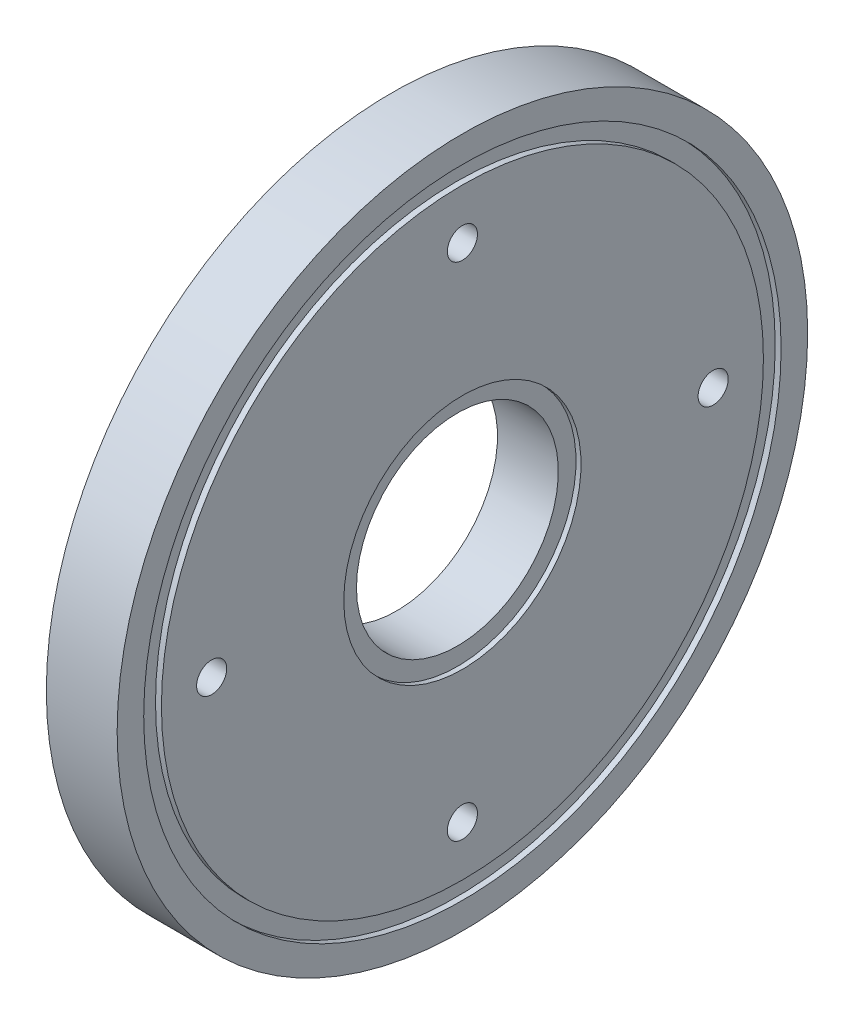
SolidWorks part; units mm, degrees
ref_plane "Front Plane" through (0, 0, 0) normal (0, 0, 1) x (1, 0, 0)
ref_plane "Top Plane" through (0, 0, 0) normal (0, 1, 0) x (1, 0, 0)
ref_plane "Right Plane" through (0, 0, 0) normal (1, 0, 0) x (0, 0, -1)
sketch "Sketch1" plane through (0, 0, 0) normal (0, 0, 1) x (1, 0, 0)
  line L0 (-801.9206, 0) -> (36107.5283, 0) construction
  line L10 (21.0477, 13.4) -> (21.0477, 39)
  line L12 (21.0477, 39) -> (13.0477, 39)
  line L16 (21.0477, 13.4) -> (20.4817, 13.4)
  line L17 (20.4817, 13.4) -> (20.4817, 11.4)
  line L18 (13.0477, 39) -> (13.0477, 13.4)
  line L22 (18.4817, 11.4) -> (20.4817, 11.4)
  line L28 (13.0477, 13.4) -> (13.6137, 13.4)
  line L29 (13.6137, 13.4) -> (13.6137, 11.4)
  line L30 (13.6137, 11.4) -> (18.4817, 11.4)
  line L31 (21.0477, 36) -> (20.3807, 36)
  line L32 (20.3807, 36) -> (20.3807, 34)
  line L33 (20.3807, 34) -> (21.0477, 34)
  line L34 (13.0477, 36) -> (13.7147, 36)
  line L35 (13.7147, 36) -> (13.7147, 34)
  line L36 (13.7147, 34) -> (13.0477, 34)
  dimension "D1" = 8
  dimension "D5" = 39
  dimension "D2" = 36
  dimension "D3" = 0.566
  dimension "D4" = 2
  dimension "D6" = 0.667
  dimension "D8" = 13.4
  dimension "D9" = 2
  dimension "D10" = 2
revolve "Revolve17" add sketch "Sketch1" angle 360 about L0 region at (17.0477, 25.2131, 0)
sketch "Sketch4" plane through (13.0477, 0, 0) normal (-1, 0, 0) x (0, 0, 1)
  circle A0 centre (0, 0) radius 28.325 construction
  point P3 (0, 28.325)
  point P7 (28.325, 0)
  point P12 (-28.325, 0)
  point P13 (0, -28.325)
  dimension "D1" = 56.65
hole_wizard "M3 Clearance Hole1" positions "Sketch4" profile "Sketch5" hole size "M3" standard "ISO"
sketch "Sketch5" plane through (13.0477, -28.325, 0) normal (0, 1, 0) x (0, 0, 1)
  line L0 (0, 0) -> (0, 9.0215)
  line L1 (0, 9.0215) -> (1.7, 8)
  line L2 (1.7, 8) -> (1.7, 0)
  line L5 (1.7, 0) -> (0, 0)
  line L10 (0, 9.0215) -> (-1.7, 8) construction
  line L11 (0, -6.35) -> (0, 107.95) construction
  dimension "Hole Dia." = 3.4
  dimension "Hole Depth" = 8
  dimension "Drill Angle" = 118
